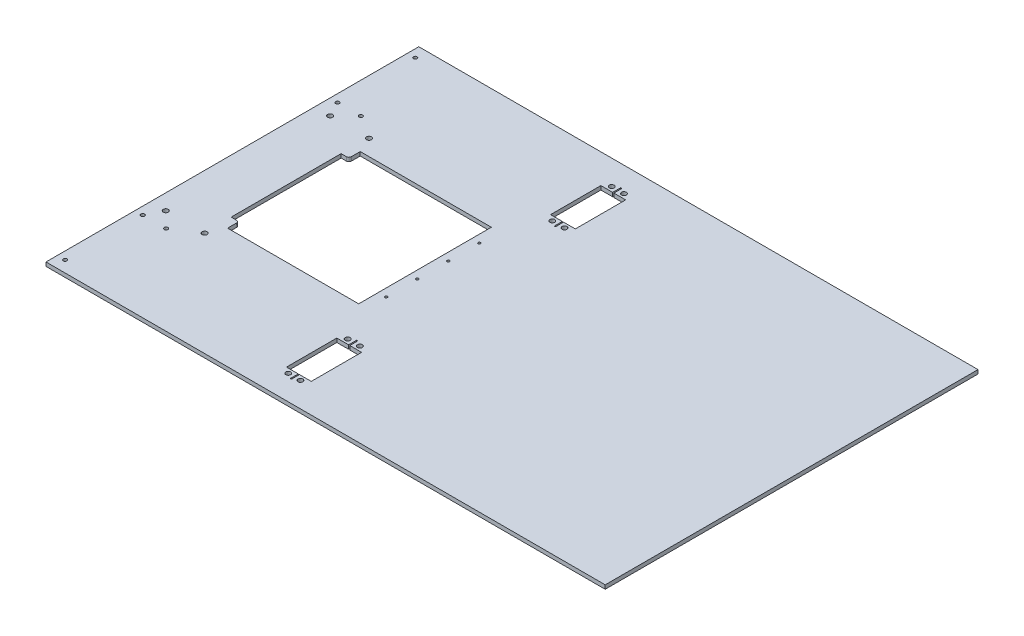
SolidWorks part; units mm, degrees
ref_plane "Front Plane" through (0, 0, 0) normal (0, 0, 1) x (1, 0, 0)
ref_plane "Top Plane" through (0, 0, 0) normal (0, 1, 0) x (1, 0, 0)
ref_plane "Right Plane" through (0, 0, 0) normal (1, 0, 0) x (0, 0, -1)
sketch "Sketch1" plane through (0, 0, 0) normal (0, 1, 0) x (1, 0, 0)
  line L1 (-228.6, -152.4) -> (228.6, -152.4)
  line L2 (-228.6, -152.4) -> (-228.6, 152.4)
  line L3 (-228.6, 152.4) -> (228.6, 152.4)
  line L4 (228.6, -152.4) -> (228.6, 152.4)
  line L5 (-228.6, -152.4) -> (228.6, 152.4) construction
  line L6 (-228.6, 152.4) -> (228.6, -152.4) construction
  point P0 (0, 0)
  dimension "D1" = 304.8
  dimension "D2" = 457.2
extrude "Boss-Extrude1" add sketch "Sketch1" along normal blind 3.175 contours L3 L4 L1 L2
sketch "Sketch2" plane through (0, 3.175, 0) normal (0, 1, 0) x (1, 0, 0)
  circle A0 centre (-184.15, -67.1976) radius 2.0635 construction
  circle A1 centre (-215.9, -67.1976) radius 2.0635 construction
  circle A2 centre (-184.15, 67.1976) radius 2.0635 construction
  circle A3 centre (-215.9, 67.1976) radius 2.0635 construction
  circle A6 centre (-184.15, -67.1976) radius 2.0635
  circle A7 centre (-215.9, -67.1976) radius 2.0635
  circle A8 centre (-184.15, 67.1976) radius 2.0635
  circle A9 centre (-215.9, 67.1976) radius 2.0635
extrude "Cut-Extrude1" cut sketch "Sketch2" against normal through all
sketch "Sketch3" plane through (0, 3.175, 0) normal (0, 1, 0) x (1, 0, 0)
  line L0 (-228.6, 0) -> (228.6, 0) construction
  line L1 (-228.6, -152.4) -> (-228.6, 152.4) construction
  line L2 (228.6, -152.4) -> (228.6, 152.4) construction
sketch "Sketch4" plane through (0, 3.175, 0) normal (0, 1, 0) x (1, 0, 0)
  line L0 (-184.658, 44.958) -> (-184.658, -44.958)
  line L1 (-184.658, -44.958) -> (-180.34, -44.958)
  line L2 (-178.308, -46.99) -> (-178.308, -54.229)
  line L3 (-178.308, -54.229) -> (-71.12, -54.229)
  line L4 (-71.12, -54.229) -> (-71.12, 54.229)
  line L5 (-71.12, 54.229) -> (-178.308, 54.229)
  line L6 (-178.308, 54.229) -> (-178.308, 46.99)
  line L7 (-180.34, 44.958) -> (-184.658, 44.958)
  line L8 (-184.15, 44.45) -> (-184.15, -44.45)
  line L9 (-180.34, 44.45) -> (-184.15, 44.45)
  line L10 (-177.8, 53.721) -> (-177.8, 46.99)
  line L11 (-71.628, 53.721) -> (-177.8, 53.721)
  line L12 (-71.628, -53.721) -> (-71.628, 53.721)
  line L13 (-177.8, -53.721) -> (-71.628, -53.721)
  line L14 (-177.8, -46.99) -> (-177.8, -53.721)
  line L15 (-184.15, -44.45) -> (-180.34, -44.45)
  line L16 (-184.15, 44.45) -> (-184.15, -44.45) construction
  line L17 (-180.34, 44.45) -> (-184.15, 44.45) construction
  line L18 (-177.8, 53.721) -> (-177.8, 46.99) construction
  line L19 (-71.628, 53.721) -> (-177.8, 53.721) construction
  line L20 (-71.628, -53.721) -> (-71.628, 53.721) construction
  line L21 (-177.8, -53.721) -> (-71.628, -53.721) construction
  line L22 (-177.8, -46.99) -> (-177.8, -53.721) construction
  line L23 (-184.15, -44.45) -> (-180.34, -44.45) construction
  arc A0 (-178.308, -46.99) -> (-180.34, -44.958) centre (-180.34, -46.99) ccw
  arc A1 (-180.34, 44.958) -> (-178.308, 46.99) centre (-180.34, 46.99) ccw
  arc A2 (-180.34, 44.45) -> (-177.8, 46.99) centre (-180.34, 46.99) ccw
  arc A3 (-177.8, -46.99) -> (-180.34, -44.45) centre (-180.34, -46.99) ccw
  arc A4 (-180.34, 44.45) -> (-177.8, 46.99) centre (-180.34, 46.99) ccw construction
  arc A5 (-177.8, -46.99) -> (-180.34, -44.45) centre (-180.34, -46.99) ccw construction
  dimension "D1" = 0
  dimension "D2" = 0.508
extrude "Cut-Extrude2" cut sketch "Sketch4" against normal up to next
sketch "Sketch5" plane through (0, 3.175, 0) normal (0, 1, 0) x (1, 0, 0)
  circle A0 centre (-203.2, 79.629) radius 1.5 construction
  circle A1 centre (-222.25, 143.129) radius 1.5 construction
  circle A2 centre (-222.25, 79.629) radius 1.5 construction
  circle A3 centre (-203.2, -79.629) radius 1.5 construction
  circle A4 centre (-222.25, -79.629) radius 1.5 construction
  circle A5 centre (-222.25, -143.129) radius 1.5 construction
  circle A6 centre (-203.2, 79.629) radius 1.5
  circle A7 centre (-222.25, 143.129) radius 1.5
  circle A8 centre (-222.25, 79.629) radius 1.5
  circle A9 centre (-203.2, -79.629) radius 1.5
  circle A10 centre (-222.25, -79.629) radius 1.5
  circle A11 centre (-222.25, -143.129) radius 1.5
extrude "Cut-Extrude3" cut sketch "Sketch5" against normal through all
sketch "Sketch7" plane through (0, 3.175, 0) normal (0, 1, 0) x (1, 0, 0)
  line L0 (-55.847, -87.373) -> (-35.593, -128.527) construction
  line L1 (-55.847, -87.373) -> (-46.22, -87.373)
  line L2 (-55.847, -87.373) -> (-55.847, -128.527)
  line L3 (-55.847, -128.527) -> (-46.22, -128.527)
  line L4 (-35.593, -87.373) -> (-35.593, -128.527)
  line L5 (-35.593, -87.373) -> (-55.847, -128.527) construction
  line L6 (-50.72, -83.65) -> (-40.72, -132.25) construction
  line L7 (-50.72, -132.25) -> (-40.72, -83.65) construction
  line L9 (-228.6, -152.4) -> (228.6, -152.4) construction
  line L10 (-45.22, -128.527) -> (-35.593, -128.527)
  line L12 (-46.22, -128.527) -> (-46.22, -135.131)
  line L13 (-46.22, -135.131) -> (-45.22, -135.131)
  line L14 (-45.22, -128.527) -> (-45.22, -135.131)
  line L15 (-45.72, -107.95) -> (-2.6371, -107.95) construction
  line L16 (-46.22, -80.769) -> (-45.22, -80.769)
  line L17 (-46.22, -87.373) -> (-46.22, -80.769)
  line L18 (-45.22, -87.373) -> (-45.22, -80.769)
  line L19 (-45.22, -87.373) -> (-35.593, -87.373)
  line L20 (-228.6, -152.4) -> (-228.6, 152.4) construction
  circle A0 centre (-50.72, -132.25) radius 2
  circle A1 centre (-40.72, -132.25) radius 2
  circle A2 centre (-50.72, -83.65) radius 2
  circle A3 centre (-40.72, -83.65) radius 2
  point P8 (-45.72, -135.131)
  point P17 (-45.72, -107.95)
  point P18 (-45.72, -107.95)
  dimension "D1" = 41.154
  dimension "D3" = 20.254
  dimension "D5" = 4
  dimension "D6" = 44.45
  dimension "D2" = 10
  dimension "D4" = 48.6
  dimension "D7" = 1
  dimension "D8" = 6.604
  dimension "D9" = 182.88
extrude "Cut-Extrude5" cut sketch "Sketch7" against normal through all
mirror "Mirror1" about plane through (0, 0, 0) normal (0, 0, 1) of "Cut-Extrude5"
sketch "Sketch8" plane through (0, 3.175, 0) normal (0, 1, 0) x (1, 0, 0)
  circle A1 centre (-64.77, -38.1) radius 1
  circle A2 centre (-64.77, -38.1) radius 1
  circle A3 centre (-64.77, -12.7) radius 1
  circle A4 centre (-64.77, -12.7) radius 1
  circle A5 centre (-64.77, 12.7) radius 1
  circle A6 centre (-64.77, 12.7) radius 1
  circle A7 centre (-64.77, 38.1) radius 1
  circle A8 centre (-64.77, 38.1) radius 1
  dimension "D1" = 0
  dimension "D2" = 0
  dimension "D3" = 0
  dimension "D4" = 0
extrude "Cut-Extrude6" cut sketch "Sketch8" against normal through all
equation "\"tightTol\" = 0.005in"
equation "\"normTol\"= 0.01in"
equation "\"looseTol\"= 0.02in"
equation "\"D2@Sketch4\"=\"looseTol\""
